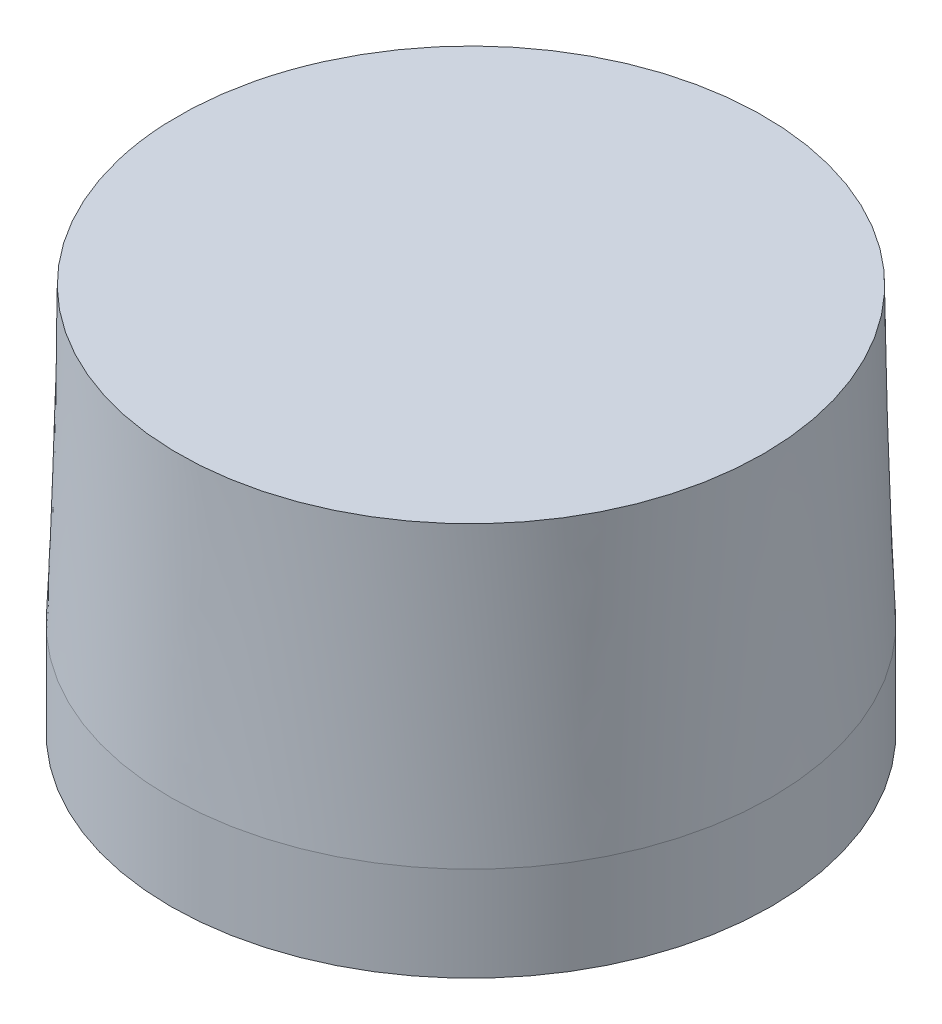
SolidWorks part; units mm, degrees
ref_plane "Front Plane" through (0, 0, 0) normal (0, 0, 1) x (1, 0, 0)
ref_plane "Top Plane" through (0, 0, 0) normal (0, 1, 0) x (1, 0, 0)
ref_plane "Right Plane" through (0, 0, 0) normal (1, 0, 0) x (0, 0, -1)
sketch "Sketch33" plane through (0, 0, 0) normal (0, 1, 0) x (1, 0, 0)
  circle A0 centre (0, 0) radius 27.9
  circle A1 centre (0, 0) radius 28.65
  circle A2 centre (0, 0) radius 26.9
extrude "Boss-Extrude6" add sketch "Sketch33" along normal blind 33 contours A0 A2 region at (-27.1109, 0, 0)
extrude "Boss-Extrude7" add sketch "Sketch33<6>" against normal blind 4 separate body contours A1 A0 region at (-28.569, 0, 0)
sketch "Sketch33<6>" plane through (0, 0, 0) normal (0, 1, 0) x (1, 0, 0) same geometry as "Sketch33"
extrude "Boss-Extrude9" add sketch "Sketch33<8>" along normal blind 5 contours A1 A0 region at (-28.569, 0, 0)
sketch "Sketch33<8>" plane through (0, 0, 0) normal (0, 1, 0) x (1, 0, 0) same geometry as "Sketch33"
extrude "Boss-Extrude10" add sketch "Sketch33<9>" along normal blind 1 from offset 22 contours A2 | A0 A2 region at (-27.1109, 0, 0) region at (0, 0, 0)
sketch "Sketch33<9>" plane through (0, 0, 0) normal (0, 1, 0) x (1, 0, 0) same geometry as "Sketch33"
loft "Loft2" add section edge at (0, 33, 27.9) section edge at (0, 5, 28.65) connector at (27.7795, 33, 2.5907) connector at (27.5719, 5, 7.7854)
sketch "Sketch36" plane through (0, 5, 0) normal (0, -1, 0) x (1, 0, 0)
  circle A0 centre (0, 0) radius 26
  circle M1 centre (0, 0) radius 26.9
extrude "Cut-Extrude1" cut sketch "Sketch36" against normal blind 27.25 contours A0 M1 | A0 region at (0, 5, 0) region at (-26.1392, 5, 0)
sketch "Sketch37" plane through (0, 32.25, 0) normal (0, -1, 0) x (1, 0, 0)
  line L0 (26.9, 0) -> (26.9, -19.7943) construction
  line L1 (14.65, 22.5608) -> (14.65, 13.0304)
  line L2 (14.65, 13.0304) -> (13.9, 13.0304)
  line L3 (13.9, 13.0304) -> (13.9, 23.0304)
  arc A1 (14.65, 22.5608) -> (13.9, 23.0304) centre (0, 0) ccw
  circle A4 centre (0, 0) radius 26.9 construction
  dimension "D3" = 12.25
  dimension "D4" = 0.75
  dimension "D5" = 10
extrude "Boss-Extrude11" add sketch "Sketch37" along normal blind 28
mirror "Mirror1" about plane through (0, 0, 0) normal (0, 0, 1) of "Boss-Extrude11"
sketch "Sketch39" plane through (13.9, 0, 0) normal (-1, 0, 0) x (0, 0, 1)
  line L0 (-13.0304, 4.25) -> (-13.0304, 32.25) construction
  line L1 (-13.0304, 20.1339) -> (-14.9002, 20.1339)
  line L2 (-13.0304, 20.1339) -> (-13.0304, 16.6339)
  line L3 (-13.0304, 16.6339) -> (-14.9002, 16.6339)
  arc A0 (-14.9002, 20.1339) -> (-14.9002, 16.6339) centre (-14.9002, 18.3839) ccw
extrude "Cut-Extrude2" cut sketch "Sketch39" against normal blind 2
